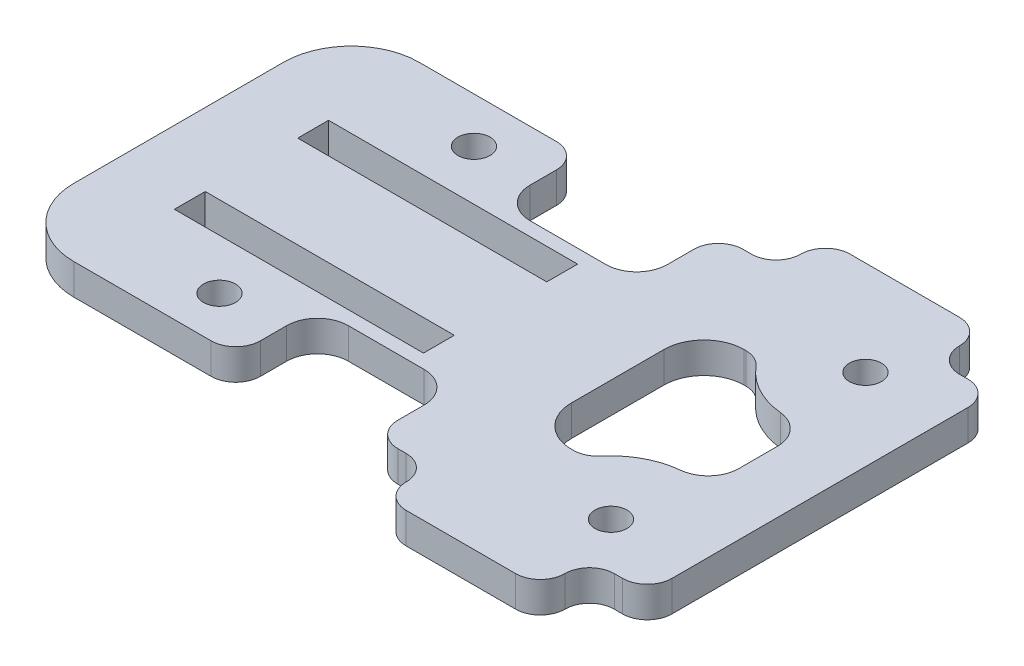
SolidWorks part; units mm, degrees
other "下垫片"
ref_plane "前视基准面" through (0, 0, 0) normal (0, 0, 1) x (1, 0, 0)
ref_plane "上视基准面" through (0, 0, 0) normal (0, 1, 0) x (1, 0, 0)
ref_plane "右视基准面" through (0, 0, 0) normal (1, 0, 0) x (0, 0, -1)
other "Configuration Table"
sketch "草图1" plane through (0, 0, 0) normal (0, 1, 0) x (1, 0, 0)
  line L0 (-89.3251, 0) -> (102.0425, 0) construction
  line L1 (0, 56.7239) -> (0, -62.578) construction
  line L2 (-47.2, -7.5) -> (-6.8, -7.5)
  line L3 (-47.2, 12.5) -> (-6.8, 12.5)
  line L4 (-47.2, 12.5) -> (-47.2, 7.5)
  line L5 (-47.2, 7.5) -> (-6.8, 7.5)
  line L6 (-6.8, 12.5) -> (-6.8, 7.5)
  line L7 (-47.2, 12.5) -> (-6.8, 7.5) construction
  line L8 (-47.2, 7.5) -> (-6.8, 12.5) construction
  line L9 (-6.8, -12.5) -> (-6.8, -7.5)
  line L10 (-47.2, -12.5) -> (-6.8, -12.5)
  line L11 (-47.2, -12.5) -> (-47.2, -7.5)
  line L14 (-21.75, -26.5375) -> (-21.75, -14.7375)
  line L15 (-21.75, -14.7375) -> (0.55, -14.7375)
  line L16 (0.55, -26.5375) -> (0.55, -14.7375)
  line L17 (-21.75, -26.5375) -> (0.55, -14.7375) construction
  line L18 (-21.75, -14.7375) -> (0.55, -26.5375) construction
  line L19 (-21.75, 14.7375) -> (0.55, 14.7375)
  line L20 (0.55, 26.5375) -> (0.55, 14.7375)
  line L22 (-21.75, 26.5375) -> (-21.75, 14.7375)
  line L23 (-21.75, 30.0095) -> (0.55, 30.0095)
  line L25 (-21.75, -26.5375) -> (-21.75, -30.0095)
  line L26 (-21.75, -30.0095) -> (0.55, -30.0095)
  line L27 (0.55, -26.5375) -> (0.55, -30.0095)
  line L28 (0.55, 26.5375) -> (0.55, 30.0095)
  line L30 (-21.75, 26.5375) -> (-21.75, 30.0095)
  circle A0 centre (-31.75, 20.6375) radius 2.6
  circle A4 centre (31.75, 20.6375) radius 2.6
  circle A5 centre (31.75, -20.6375) radius 2.6
  circle A6 centre (-31.75, -20.6375) radius 2.6
  point P13 (-27, 10)
  point P22 (-10.6, -20.6375)
  point P35 (-27, 10)
  dimension "D5" = 5.2
  dimension "D11" = 5.2
  dimension "D1" = 40.4
  dimension "D2" = 31.75
  dimension "D3" = 5
  dimension "D4" = 20.6375
  dimension "D6" = 10
  dimension "D7" = 22.3
  dimension "D8" = 11.8
  dimension "D9" = 0
  dimension "D10" = 31.2
  dimension "D12" = 5
  dimension "D13" = 40.4
  dimension "D14" = 27
  dimension "D15" = 10
  dimension "D16" = 2.2375
sketch "草图3" plane through (0, 0, 0) normal (0, 1, 0) x (1, 0, 0)
  line L0 (-40, 28) -> (-59, 28)
  line L1 (-40, -28) -> (9.9, -28)
  line L3 (-40, 28) -> (9.9, 28)
  line L5 (-40, -28) -> (40, 28) construction
  line L6 (-40, 28) -> (40, -28) construction
  line L7 (-59, 28) -> (-59, -28)
  line L8 (-59, -28) -> (-40, -28)
  line L10 (45, 28) -> (45, -28)
  line L15 (-45.7746, 0) -> (58.2399, 0) construction
  line L19 (9.9, 28) -> (9.9, 36)
  line L20 (9.9, 36) -> (35.65, 36)
  line L21 (35.65, 36) -> (35.65, 28)
  line L22 (35.65, 28) -> (45, 28)
  line L23 (35.65, -28) -> (45, -28)
  line L24 (35.65, -36) -> (35.65, -28)
  line L25 (9.9, -36) -> (35.65, -36)
  line L26 (9.9, -28) -> (9.9, -36)
  point P0 (0, 0)
  dimension "D1" = 56
  dimension "D2" = 80
  dimension "D3" = 19
  dimension "D4" = 5
  dimension "D5" = 9.35
  dimension "D6" = 8
  dimension "D7" = 25.75
extrude "凸台-拉伸1" add sketch "草图3" along normal blind 5
extrude "切除-拉伸1" cut sketch "草图1" along normal up to surface (5 mm away) up to face at (12.85, 5, 0)
fillet "圆角1" radius 5 4 edges at (0.55, 2.5, 14.7375) (-21.75, 2.5, 14.7375) (0.55, 2.5, -14.7375) (-21.75, 2.5, -14.7375)
fillet "圆角2" radius 4 14 edges at (0.55, 2.5, 28) (-21.75, 2.5, 28) (0.55, 2.5, -28) (-21.75, 2.5, -28) (9.9, 2.5, 28) (9.9, 2.5, 36) (35.65, 2.5, 36) (35.65, 2.5, 28) (45, 2.5, 28) (45, 2.5, -28) (35.65, 2.5, -28) (35.65, 2.5, -36) (9.9, 2.5, -36) (9.9, 2.5, -28)
sketch "草图14" plane through (0, 5, 0) normal (0, 1, 0) x (1, 0, 0)
  line L0 (-11.6114, 0) -> (10.899, 0) construction
  line L1 (21.04, 14) -> (12.2, 14)
  line L2 (12.2, 14) -> (12.2, -14)
  line L3 (45, -24) -> (45, 24) construction
  line L4 (35, 8.4639) -> (35, -8.4639)
  line L5 (21.04, -14) -> (12.2, -14)
  arc A0 (35, 8.4639) -> (21.04, 14) centre (31.75, 20.6375) cw
  arc A1 (35, -8.4639) -> (21.04, -14) centre (31.75, -20.6375) ccw
  point P5 (35, 0)
  point P7 (21.04, 14)
  point P8 (35, 8.4639)
  point P18 (12.2, 0)
  dimension "D1" = 12.6
  dimension "D2" = 14
  dimension "D3" = 12.2
  dimension "D4" = 10
extrude "切除-拉伸6" cut sketch "草图14" against normal through all
fillet "圆角5" radius 4 2 edges at (21.04, 2.5, 14) (21.04, 2.5, -14)
fillet "圆角6" radius 11 2 edges at (-59, 2.5, 28) (-59, 2.5, -28)
fillet "圆角7" radius 6.5 2 edges at (12.2, 2.5, 14) (12.2, 2.5, -14)
fillet "圆角8" radius 5 2 edges at (35, 2.5, 8.4639) (35, 2.5, -8.4639)
